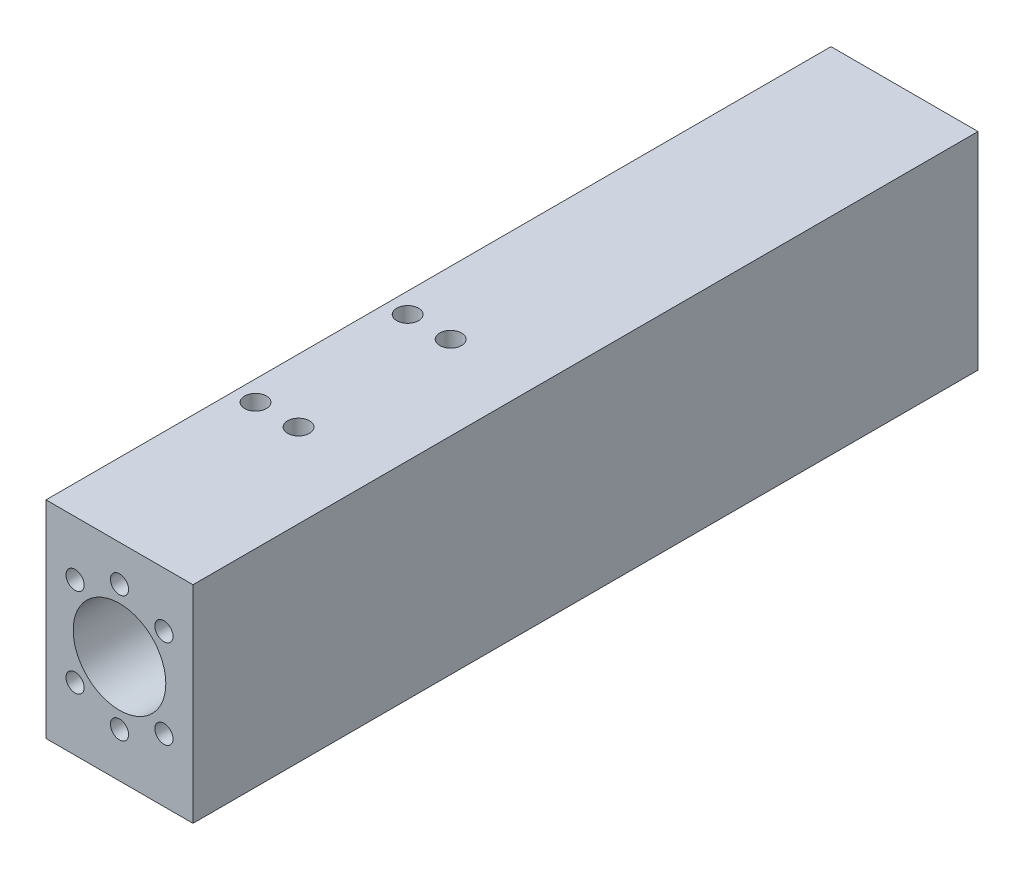
SolidWorks part; units mm, degrees
ref_plane "Front" through (0, 0, 0) normal (0, 0, 1) x (1, 0, 0)
ref_plane "Top" through (0, 0, 0) normal (0, 1, 0) x (1, 0, 0)
ref_plane "Right" through (0, 0, 0) normal (1, 0, 0) x (0, 0, -1)
sketch "Sketch1" plane through (0, 0, 0) normal (0, 0, 1) x (1, 0, 0)
  line L1 (0, 0) -> (44.45, 0)
  line L2 (0, 0) -> (0, 62.5)
  line L3 (0, 62.5) -> (44.45, 62.5)
  line L4 (44.45, 0) -> (44.45, 62.5)
  dimension "D1" = 44.45
  dimension "D2" = 62.5
extrude "Boss-Extrude1" add sketch "Sketch1" along normal blind 237.38
sketch "Sketch2" plane through (0, 0, 237.38) normal (0, 0, 1) x (1, 0, 0)
  arc A0 (14.225, 32.5) -> (30.225, 32.5) centre (22.225, 32.5) ccw construction
  arc A1 (30.225, 32.5) -> (14.225, 32.5) centre (22.225, 32.5) ccw construction
  arc A2 (14.225, 32.5) -> (30.225, 32.5) centre (22.225, 32.5) ccw
  arc A3 (30.225, 32.5) -> (14.225, 32.5) centre (22.225, 32.5) ccw
  arc A4 (38.41, 45.935) -> (32.91, 45.935) centre (35.66, 45.935) ccw construction
  arc A5 (38.41, 45.935) -> (32.91, 45.935) centre (35.66, 45.935) ccw construction
  arc A6 (38.41, 19.065) -> (32.91, 19.065) centre (35.66, 19.065) ccw construction
  arc A7 (38.41, 19.065) -> (32.91, 19.065) centre (35.66, 19.065) ccw construction
  arc A8 (24.975, 13.5) -> (19.475, 13.5) centre (22.225, 13.5) ccw construction
  arc A9 (24.975, 13.5) -> (19.475, 13.5) centre (22.225, 13.5) ccw construction
  arc A10 (11.54, 19.065) -> (6.04, 19.065) centre (8.79, 19.065) ccw construction
  arc A11 (11.54, 19.065) -> (6.04, 19.065) centre (8.79, 19.065) ccw construction
  arc A12 (11.54, 45.935) -> (6.04, 45.935) centre (8.79, 45.935) ccw construction
  arc A13 (11.54, 45.935) -> (6.04, 45.935) centre (8.79, 45.935) ccw construction
  arc A14 (24.975, 51.5) -> (19.475, 51.5) centre (22.225, 51.5) ccw construction
  arc A15 (24.975, 51.5) -> (19.475, 51.5) centre (22.225, 51.5) ccw construction
  arc A16 (32.91, 19.065) -> (38.41, 19.065) centre (35.66, 19.065) ccw construction
  arc A17 (32.91, 19.065) -> (38.41, 19.065) centre (35.66, 19.065) ccw construction
  arc A18 (19.475, 13.5) -> (24.975, 13.5) centre (22.225, 13.5) ccw construction
  arc A19 (19.475, 13.5) -> (24.975, 13.5) centre (22.225, 13.5) ccw construction
  arc A20 (6.04, 19.065) -> (11.54, 19.065) centre (8.79, 19.065) ccw construction
  arc A21 (6.04, 19.065) -> (11.54, 19.065) centre (8.79, 19.065) ccw construction
  arc A22 (32.91, 45.935) -> (38.41, 45.935) centre (35.66, 45.935) ccw construction
  arc A23 (32.91, 45.935) -> (38.41, 45.935) centre (35.66, 45.935) ccw construction
  arc A24 (19.475, 51.5) -> (24.975, 51.5) centre (22.225, 51.5) ccw construction
  arc A25 (19.475, 51.5) -> (24.975, 51.5) centre (22.225, 51.5) ccw construction
  arc A26 (6.04, 45.935) -> (11.54, 45.935) centre (8.79, 45.935) ccw construction
  arc A27 (6.04, 45.935) -> (11.54, 45.935) centre (8.79, 45.935) ccw construction
  arc A28 (38.41, 45.935) -> (32.91, 45.935) centre (35.66, 45.935) ccw
  arc A29 (38.41, 45.935) -> (32.91, 45.935) centre (35.66, 45.935) ccw
  arc A30 (38.41, 19.065) -> (32.91, 19.065) centre (35.66, 19.065) ccw
  arc A31 (38.41, 19.065) -> (32.91, 19.065) centre (35.66, 19.065) ccw
  arc A32 (24.975, 13.5) -> (19.475, 13.5) centre (22.225, 13.5) ccw
  arc A33 (24.975, 13.5) -> (19.475, 13.5) centre (22.225, 13.5) ccw
  arc A34 (11.54, 19.065) -> (6.04, 19.065) centre (8.79, 19.065) ccw
  arc A35 (11.54, 19.065) -> (6.04, 19.065) centre (8.79, 19.065) ccw
  arc A36 (11.54, 45.935) -> (6.04, 45.935) centre (8.79, 45.935) ccw
  arc A37 (11.54, 45.935) -> (6.04, 45.935) centre (8.79, 45.935) ccw
  arc A38 (24.975, 51.5) -> (19.475, 51.5) centre (22.225, 51.5) ccw
  arc A39 (24.975, 51.5) -> (19.475, 51.5) centre (22.225, 51.5) ccw
  arc A40 (32.91, 19.065) -> (38.41, 19.065) centre (35.66, 19.065) ccw
  arc A41 (32.91, 19.065) -> (38.41, 19.065) centre (35.66, 19.065) ccw
  arc A42 (19.475, 13.5) -> (24.975, 13.5) centre (22.225, 13.5) ccw
  arc A43 (19.475, 13.5) -> (24.975, 13.5) centre (22.225, 13.5) ccw
  arc A44 (6.04, 19.065) -> (11.54, 19.065) centre (8.79, 19.065) ccw
  arc A45 (6.04, 19.065) -> (11.54, 19.065) centre (8.79, 19.065) ccw
  arc A46 (32.91, 45.935) -> (38.41, 45.935) centre (35.66, 45.935) ccw
  arc A47 (32.91, 45.935) -> (38.41, 45.935) centre (35.66, 45.935) ccw
  arc A48 (19.475, 51.5) -> (24.975, 51.5) centre (22.225, 51.5) ccw
  arc A49 (19.475, 51.5) -> (24.975, 51.5) centre (22.225, 51.5) ccw
  arc A50 (6.04, 45.935) -> (11.54, 45.935) centre (8.79, 45.935) ccw
  arc A51 (6.04, 45.935) -> (11.54, 45.935) centre (8.79, 45.935) ccw
  arc A52 (8.225, 32.5) -> (36.225, 32.5) centre (22.225, 32.5) ccw construction
  arc A53 (8.225, 32.5) -> (36.225, 32.5) centre (22.225, 32.5) ccw construction
  arc A54 (36.225, 32.5) -> (8.225, 32.5) centre (22.225, 32.5) ccw construction
  arc A55 (36.225, 32.5) -> (8.225, 32.5) centre (22.225, 32.5) ccw construction
  arc A56 (8.225, 32.5) -> (36.225, 32.5) centre (22.225, 32.5) ccw
  arc A57 (8.225, 32.5) -> (36.225, 32.5) centre (22.225, 32.5) ccw
  arc A58 (36.225, 32.5) -> (8.225, 32.5) centre (22.225, 32.5) ccw
  arc A59 (36.225, 32.5) -> (8.225, 32.5) centre (22.225, 32.5) ccw
extrude "Cut-Extrude1" cut sketch "Sketch2" against normal through all contours A2 A3 region at (22.225, 32.5, 237.38)
extrude "Cut-Extrude2" cut sketch "Sketch2<4>" against normal blind 32 contours A56 A58 A3 A2 region at (22.225, 46.104, 237.38)
sketch "Sketch2<4>" plane through (0, 0, 237.38) normal (0, 0, 1) x (1, 0, 0) same geometry as "Sketch2"
extrude "Cut-Extrude3" cut sketch "Sketch2<5>" against normal blind 12.7 contours A36 A50 | A38 A48 | A28 A46 | A30 A40 | A32 A42 | A34 A44 region at (35.66, 45.935, 237.38) region at (35.66, 19.065, 237.38) region at (22.225, 13.5, 237.38) region at (8.79, 19.065, 237.38) region at (8.79, 45.935, 237.38) region at (22.225, 51.5, 237.38)
sketch "Sketch2<5>" plane through (0, 0, 237.38) normal (0, 0, 1) x (1, 0, 0) same geometry as "Sketch2"
sketch "Sketch4" plane through (0, 0, 0) normal (-1, 0, 0) x (0, 0, 1)
  circle A0 centre (157.1449, 35.325) radius 3.175 construction
  circle A1 centre (157.1449, 54.375) radius 3.175 construction
  circle A2 centre (157.1449, 35.325) radius 3.175
  circle A3 centre (157.1449, 54.375) radius 3.175
  arc A4 (41.4, 55.1) -> (39.3489, 52.5494) centre (41.4, 53) ccw construction
  arc A5 (41.4, 50.9) -> (41.4, 55.1) centre (41.4, 53) ccw construction
  arc A6 (39.3489, 52.5494) -> (41.4, 50.9) centre (41.4, 53) ccw construction
  arc A7 (13.3, 53) -> (15.4, 50.9) centre (15.4, 53) ccw construction
  arc A8 (15.4, 55.1) -> (13.3, 53) centre (15.4, 53) ccw construction
  arc A9 (15.4, 50.9) -> (15.4, 55.1) centre (15.4, 53) ccw construction
  arc A10 (41.4, 55.1) -> (39.3489, 52.5494) centre (41.4, 53) ccw
  arc A11 (41.4, 50.9) -> (41.4, 55.1) centre (41.4, 53) ccw
  arc A12 (39.3489, 52.5494) -> (41.4, 50.9) centre (41.4, 53) ccw
  arc A13 (13.3, 53) -> (15.4, 50.9) centre (15.4, 53) ccw
  arc A14 (15.4, 55.1) -> (13.3, 53) centre (15.4, 53) ccw
  arc A15 (15.4, 50.9) -> (15.4, 55.1) centre (15.4, 53) ccw
  arc A16 (221.98, 50.9) -> (221.98, 55.1) centre (221.98, 53) ccw construction
  arc A17 (221.98, 55.1) -> (219.9289, 52.5494) centre (221.98, 53) ccw construction
  arc A18 (219.9289, 52.5494) -> (221.98, 50.9) centre (221.98, 53) ccw construction
  arc A19 (193.88, 53) -> (195.98, 50.9) centre (195.98, 53) ccw construction
  arc A20 (195.98, 50.9) -> (195.98, 55.1) centre (195.98, 53) ccw construction
  arc A21 (195.98, 55.1) -> (193.88, 53) centre (195.98, 53) ccw construction
  arc A22 (221.98, 50.9) -> (221.98, 55.1) centre (221.98, 53) ccw
  arc A23 (221.98, 55.1) -> (219.9289, 52.5494) centre (221.98, 53) ccw
  arc A24 (219.9289, 52.5494) -> (221.98, 50.9) centre (221.98, 53) ccw
  arc A25 (193.88, 53) -> (195.98, 50.9) centre (195.98, 53) ccw
  arc A26 (195.98, 50.9) -> (195.98, 55.1) centre (195.98, 53) ccw
  arc A27 (195.98, 55.1) -> (193.88, 53) centre (195.98, 53) ccw
  arc A28 (219.9289, 12.4506) -> (221.98, 9.9) centre (221.98, 12) ccw construction
  arc A29 (221.98, 9.9) -> (221.98, 14.1) centre (221.98, 12) ccw construction
  arc A30 (221.98, 14.1) -> (219.9289, 12.4506) centre (221.98, 12) ccw construction
  arc A31 (193.88, 12) -> (195.98, 9.9) centre (195.98, 12) ccw construction
  arc A32 (195.98, 14.1) -> (193.88, 12) centre (195.98, 12) ccw construction
  arc A33 (195.98, 9.9) -> (195.98, 14.1) centre (195.98, 12) ccw construction
  arc A34 (219.9289, 12.4506) -> (221.98, 9.9) centre (221.98, 12) ccw
  arc A35 (221.98, 9.9) -> (221.98, 14.1) centre (221.98, 12) ccw
  arc A36 (221.98, 14.1) -> (219.9289, 12.4506) centre (221.98, 12) ccw
  arc A37 (193.88, 12) -> (195.98, 9.9) centre (195.98, 12) ccw
  arc A38 (195.98, 14.1) -> (193.88, 12) centre (195.98, 12) ccw
  arc A39 (195.98, 9.9) -> (195.98, 14.1) centre (195.98, 12) ccw
  arc A40 (13.3, 12) -> (15.4, 9.9) centre (15.4, 12) ccw construction
  arc A41 (15.4, 9.9) -> (15.4, 14.1) centre (15.4, 12) ccw construction
  arc A42 (15.4, 14.1) -> (13.3, 12) centre (15.4, 12) ccw construction
  arc A43 (39.3489, 12.4506) -> (41.4, 9.9) centre (41.4, 12) ccw construction
  arc A44 (41.4, 9.9) -> (41.4, 14.1) centre (41.4, 12) ccw construction
  arc A45 (41.4, 14.1) -> (39.3489, 12.4506) centre (41.4, 12) ccw construction
  arc A46 (13.3, 12) -> (15.4, 9.9) centre (15.4, 12) ccw
  arc A47 (15.4, 9.9) -> (15.4, 14.1) centre (15.4, 12) ccw
  arc A48 (15.4, 14.1) -> (13.3, 12) centre (15.4, 12) ccw
  arc A49 (39.3489, 12.4506) -> (41.4, 9.9) centre (41.4, 12) ccw
  arc A50 (41.4, 9.9) -> (41.4, 14.1) centre (41.4, 12) ccw
  arc A51 (41.4, 14.1) -> (39.3489, 12.4506) centre (41.4, 12) ccw
extrude "Cut-Extrude4" cut sketch "Sketch4" against normal blind 6.35
sketch "Sketch5" plane through (0, 62.5, 0) normal (0, 1, 0) x (1, 0, 0)
  arc A0 (9.425, -134.1449) -> (2.825, -134.1449) centre (6.125, -134.1449) ccw construction
  arc A1 (2.825, -134.1449) -> (9.425, -134.1449) centre (6.125, -134.1449) ccw construction
  arc A2 (22.425, -134.1449) -> (15.825, -134.1449) centre (19.125, -134.1449) ccw construction
  arc A3 (15.825, -134.1449) -> (22.425, -134.1449) centre (19.125, -134.1449) ccw construction
  arc A4 (9.425, -180.1449) -> (2.825, -180.1449) centre (6.125, -180.1449) ccw construction
  arc A5 (2.825, -180.1449) -> (9.425, -180.1449) centre (6.125, -180.1449) ccw construction
  arc A6 (22.425, -180.1449) -> (15.825, -180.1449) centre (19.125, -180.1449) ccw construction
  arc A7 (15.825, -180.1449) -> (22.425, -180.1449) centre (19.125, -180.1449) ccw construction
  arc A8 (9.425, -134.1449) -> (2.825, -134.1449) centre (6.125, -134.1449) ccw
  arc A9 (2.825, -134.1449) -> (9.425, -134.1449) centre (6.125, -134.1449) ccw
  arc A10 (22.425, -134.1449) -> (15.825, -134.1449) centre (19.125, -134.1449) ccw
  arc A11 (15.825, -134.1449) -> (22.425, -134.1449) centre (19.125, -134.1449) ccw
  arc A12 (9.425, -180.1449) -> (2.825, -180.1449) centre (6.125, -180.1449) ccw
  arc A13 (2.825, -180.1449) -> (9.425, -180.1449) centre (6.125, -180.1449) ccw
  arc A14 (22.425, -180.1449) -> (15.825, -180.1449) centre (19.125, -180.1449) ccw
  arc A15 (15.825, -180.1449) -> (22.425, -180.1449) centre (19.125, -180.1449) ccw
extrude "Cut-Extrude5" cut sketch "Sketch5" against normal blind 25.4
sketch "Sketch6" plane through (0, 0, 0) normal (0, -1, 0) x (1, 0, 0)
  line L0 (22.225, 0) -> (22.225, 25.4) construction
  line L1 (0, 0) -> (44.45, 0) construction
  line L2 (22.225, 25.4) -> (22.225, 211.98) construction
  line L3 (22.225, 211.98) -> (22.225, 237.38) construction
  line L4 (0, 237.38) -> (44.45, 237.38) construction
  circle A0 centre (22.225, 211.98) radius 7.9375
  circle A1 centre (22.225, 25.4) radius 7.9375
  dimension "D2" = 15.875
  dimension "D1" = 25.4
extrude "Cut-Extrude6" cut sketch "Sketch6" against normal blind 12.7
